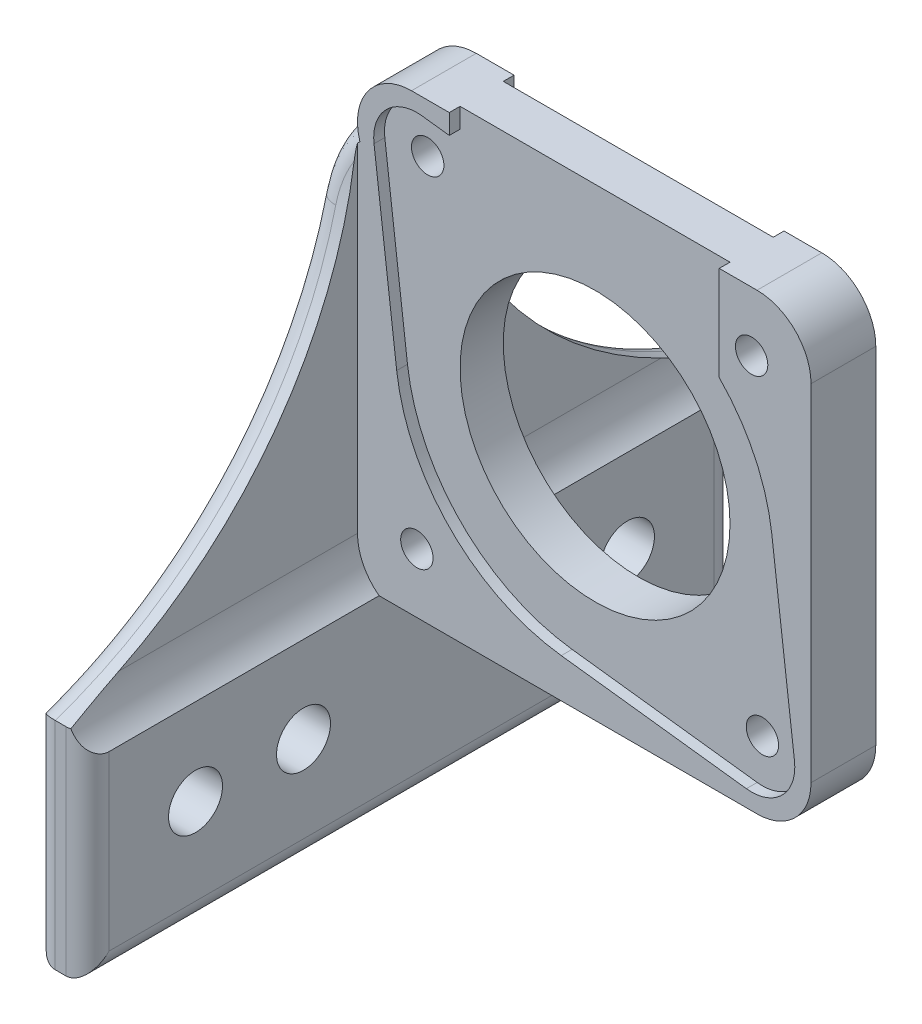
SolidWorks part; units mm, degrees
ref_plane "Front Plane" through (0, 0, 0) normal (0, 0, 1) x (1, 0, 0)
ref_plane "Top Plane" through (0, 0, 0) normal (0, 1, 0) x (1, 0, 0)
ref_plane "Right Plane" through (0, 0, 0) normal (1, 0, 0) x (0, 0, -1)
sketch "Sketch1" plane through (0, 0, 0) normal (0, 0, 1) x (1, 0, 0)
  line L0 (-15.5, 15.5) -> (15.5, 15.5) construction
  line L1 (-16, -21) -> (16, -21)
  line L2 (-21, -16) -> (-21, 16)
  line L3 (-16, 21) -> (16, 21)
  line L4 (21, -16) -> (21, 16)
  line L5 (-21, -21) -> (21, 21) construction
  line L6 (-21, 21) -> (21, -21) construction
  line L7 (-15.5, 15.5) -> (-15.5, -15.5) construction
  line L8 (-15.5, -15.5) -> (15.5, -15.5) construction
  line L9 (-21, -16) -> (-21, -21)
  line L10 (-21, -21) -> (-16, -21)
  circle A0 centre (0, 0) radius 12.5
  circle A1 centre (-15.5, 15.5) radius 1.5
  circle A2 centre (15.5, 15.5) radius 1.5
  circle A3 centre (-15.5, -15.5) radius 1.5
  circle A4 centre (15.5, -15.5) radius 1.5
  arc A5 (16, -21) -> (21, -16) centre (16, -16) ccw
  arc A6 (16, 21) -> (21, 16) centre (16, 16) cw
  arc A7 (-21, 16) -> (-16, 21) centre (-16, 16) cw
  point P0 (0, 0)
  dimension "D2" = 25
  dimension "D3" = 3
  dimension "D4" = 3
  dimension "D6" = 3
  dimension "D7" = 3
  dimension "D8" = 5
  dimension "D1" = 42
  dimension "D5" = 31
  dimension "D9" = 42
extrude "Boss-Extrude1" add sketch "Sketch1" along normal blind 3
ref_plane "Plane1" through (-21, 0, 0) normal (-1, 0, 0) x (0, 0, 1)
sketch "Sketch2" plane through (-21, 0, 0) normal (-1, 0, 0) x (0, 0, 1)
  line L1 (3, -39) -> (-27, -39)
  line L2 (-27, -39) -> (-27, -19)
  line L4 (-17, -19) -> (-17, -39) construction
  line L5 (-7, -19) -> (-7, -39) construction
  line L6 (-27, -29) -> (3, -29) construction
  line L17 (3, -39) -> (3, 16)
  line L18 (3, 16) -> (0, 16)
  arc A0 (0, 16) -> (-27, -19) centre (-39.533, 18.5826) cw
  circle A1 centre (-17, -29) radius 2.5
  circle A2 centre (-7, -29) radius 2.5
  dimension "D5" = 39.6172
  dimension "D7" = 5
  dimension "D8" = 5
  dimension "D1" = 55
  dimension "D2" = 30
  dimension "D3" = 10
  dimension "D4" = 10
  dimension "D6" = 20
extrude "Boss-Extrude2" add sketch "Sketch2" along normal blind 3 separate body
fillet "Fillet1" radius 10 1 edges at (-24, 16, 1.5)
ref_plane "Plane2" through (-21, -21, 0) normal (0, -1, 0) x (-1, 0, 0)
mirror "Mirror1" about plane through (16, -16, 3) normal (0, 0, 1) of "Boss-Extrude1", "Boss-Extrude2", "Fillet1"
sketch "Sketch3" plane through (0, 0, 6) normal (0, 0, 1) x (1, 0, 0)
  line L0 (19.4703, -15.0136) -> (17.3701, 2.1282)
  line L1 (15.0136, -19.4703) -> (-2.1282, -17.3701)
  line L2 (-15.0138, 19.4706) -> (2.1284, 17.3701)
  line L3 (-19.4706, 15.0138) -> (-17.3701, -2.1282)
  line L4 (-15.5003, 15.5003) -> (15.5, -15.5) construction
  line L5 (-12.5, 0) -> (12.5, 0) construction
  circle A0 centre (0, 0) radius 12.5
  arc A1 (-17.3701, -2.1282) -> (-2.1282, -17.3701) centre (0, 0) ccw
  arc A2 (-15.0138, 19.4706) -> (-19.4706, 15.0138) centre (-15.5003, 15.5003) ccw
  arc A3 (15.0136, -19.4703) -> (19.4703, -15.0136) centre (15.5, -15.5) ccw
  arc A4 (17.3701, 2.1282) -> (2.1284, 17.3701) centre (0, 0) ccw
  circle A7 centre (0, 0) radius 12.5 construction
  point P5 (0, 0)
  dimension "D1" = 25
  dimension "D2" = 17.5
  dimension "D3" = 8
  dimension "D4" = 8
  dimension "D5" = 43.841
  dimension "D6" = 45
  dimension "D7" = 17.1417
  dimension "D8" = 17.1417
  dimension "D9" = 17.142
extrude "Cut-Extrude1" cut sketch "Sketch3" against normal blind 1
sketch "Sketch5" plane through (0, 0, 0) normal (0, 0, 1) x (1, 0, 0)
  line L0 (19.4703, -15.0136) -> (17.3701, 2.1282)
  line L1 (15.0136, -19.4703) -> (-2.1282, -17.3701)
  line L2 (-15.0138, 19.4706) -> (2.1284, 17.3701)
  line L3 (-19.4706, 15.0138) -> (-17.3701, -2.1282)
  line L4 (-15.5003, 15.5003) -> (15.5, -15.5) construction
  line L5 (12.5, 0) -> (-12.5, 0) construction
  circle A0 centre (0, 0) radius 12.5
  arc A1 (-17.3701, -2.1282) -> (-2.1282, -17.3701) centre (0, 0) ccw
  arc A2 (-15.0138, 19.4706) -> (-19.4706, 15.0138) centre (-15.5003, 15.5003) ccw
  arc A3 (15.0136, -19.4703) -> (19.4703, -15.0136) centre (15.5, -15.5) ccw
  arc A4 (17.3701, 2.1282) -> (2.1284, 17.3701) centre (0, 0) ccw
  circle A7 centre (0, 0) radius 12.5 construction
  point P5 (0, 0)
  dimension "D1" = 25
  dimension "D2" = 17.5
  dimension "D3" = 8
  dimension "D4" = 8
  dimension "D5" = 43.841
  dimension "D6" = 45
  dimension "D7" = 17.1417
  dimension "D8" = 17.1417
  dimension "D9" = 17.142
extrude "Cut-Extrude3" cut sketch "Sketch5" along normal blind 1
sketch "Sketch6" plane through (-21, 0, 0) normal (1, 0, 0) x (0, 0, -1)
  line L0 (27, -19) -> (27, -39) construction
  line L1 (-33, -39) -> (27, -39)
  line L2 (-33, -39) -> (-33, -21)
  line L3 (-33, -21) -> (27, -21)
  line L4 (27, -39) -> (27, -21)
  line L5 (-10.175, -21) -> (10.175, -21) construction
  circle A0 centre (-23, -29) radius 2.5
  circle A1 centre (-13, -29) radius 2.5
  circle A2 centre (7, -29) radius 2.5
  circle A3 centre (17, -29) radius 2.5
  dimension "D1" = 5
extrude "Boss-Extrude3" add sketch "Sketch6" along normal blind 2
fillet "Fillet2" radius 5 2 edges at (-21, -21, -13.5) (-21, -21, 19.5)
fillet "Fillet3" radius 2 10 edges at (-23.4641, 12.0883, 6.4517) (-23.4641, 12.0883, -0.4517) (-24, -8.3771, 16.5036) (-24, -8.3771, -10.5036) (-24, -29, -27) (-19, -30, -27) (-24, -39, 3) (-19, -30, 33) (-24, -29, 33) (-19, -39, 3)
sketch "Sketch7" plane through (0, 0, 5) normal (0, 0, 1) x (1, 0, 0)
  line L0 (0, 0) -> (0, 21) construction
  line L1 (16, 21) -> (-16, 21) construction
  line L3 (12.5, 21) -> (-12.5, 21)
  line L4 (12.5, 21) -> (12.5, 0)
  line L5 (12.5, 0) -> (-12.5, 0)
  line L6 (-12.5, 21) -> (-12.5, 0)
  line L7 (12.5, 21) -> (-12.5, 0) construction
  line L8 (12.5, 0) -> (-12.5, 21) construction
  circle A0 centre (0, 0) radius 12.5 construction
  point P5 (0, 10.5)
  point P12 (0, 0)
extrude "Cut-Extrude4" cut sketch "Sketch7" along normal blind 1
sketch "Sketch8" plane through (0, 0, 1) normal (0, 0, -1) x (-1, 0, 0)
  line L0 (0, 0) -> (0, 21) construction
  line L1 (-16, 21) -> (16, 21) construction
  line L3 (12.5, 21) -> (-12.5, 21)
  line L4 (12.5, 21) -> (12.5, 0)
  line L5 (12.5, 0) -> (-12.5, 0)
  line L6 (-12.5, 21) -> (-12.5, 0)
  line L7 (12.5, 21) -> (-12.5, 0) construction
  line L8 (12.5, 0) -> (-12.5, 21) construction
  circle A0 centre (0, 0) radius 12.5 construction
  point P5 (0, 10.5)
extrude "Cut-Extrude5" cut sketch "Sketch8" along normal blind 1
